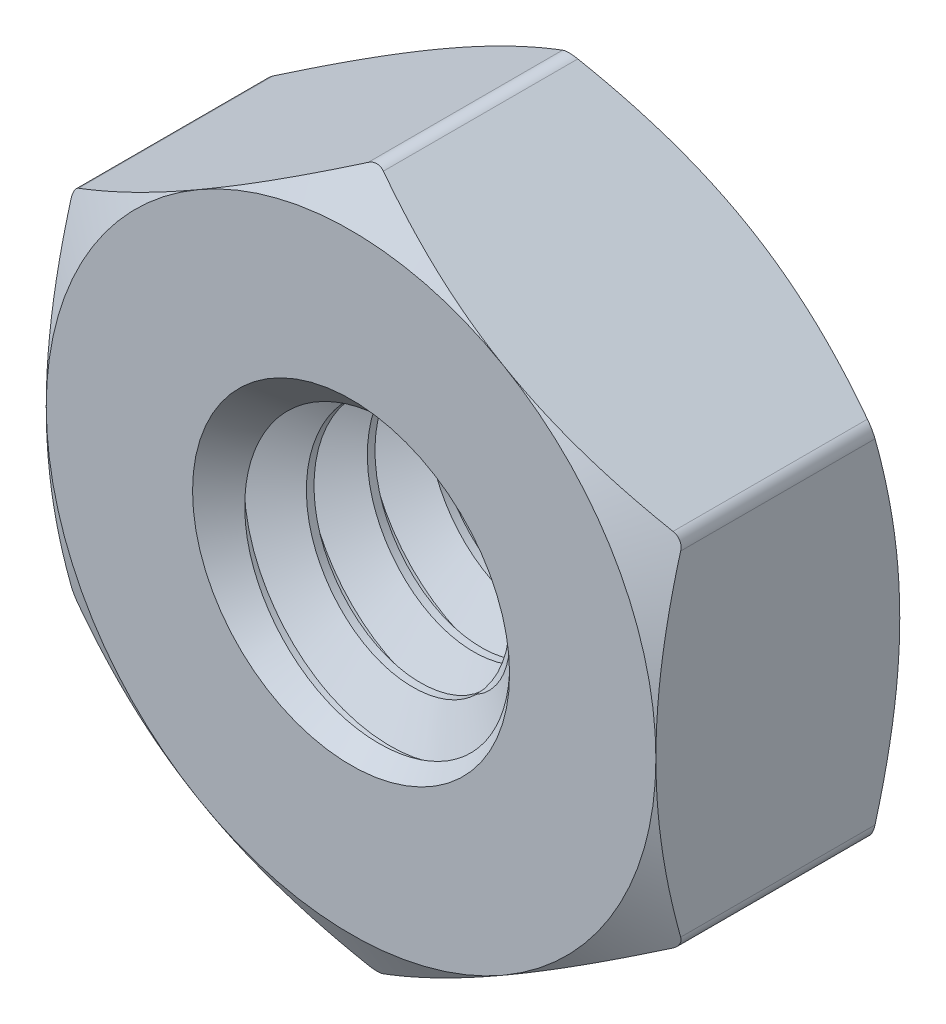
SolidWorks part; units mm, degrees
ref_plane "Front" through (0, 0, 0) normal (0, 0, 1) x (1, 0, 0)
ref_plane "Top" through (0, 0, 0) normal (0, 1, 0) x (1, 0, 0)
ref_plane "Right" through (0, 0, 0) normal (1, 0, 0) x (0, 0, -1)
sketch "Sketch1" plane through (0, 0, 0) normal (0, 0, 1) x (1, 0, 0)
  line L0 (0, 1) -> (0, 0.6) construction
  line L1 (-2, 1.1547) -> (-2, -1.1547)
  line L2 (-2, -1.1547) -> (0, -2.3094)
  line L3 (0, -2.3094) -> (2, -1.1547)
  line L4 (2, -1.1547) -> (2, 1.1547)
  line L5 (2, 1.1547) -> (0, 2.3094)
  line L6 (0, 2.3094) -> (-2, 1.1547)
  circle A0 centre (0, 0) radius 2 construction
  circle A1 centre (0, 0) radius 1 construction
  point P10 (0, 1)
  dimension "Width" = 4
  dimension "Thread Size" = 2
  dimension "Thread Pitch" = 0.4
sketch "Sketch2" plane through (0, 0, 0) normal (1, 0, 0) x (0, 0, -1)
  line L0 (-0.8, 0) -> (0.8, 0) construction
  line L1 (-0.8, 2.3094) -> (0.8, 2.3094) construction
  dimension "Height" = 1.6
sketch "Sketch15" plane through (0, 0, 0) normal (0, 0, 1) x (1, 0, 0)
  line L1 (0, 2.3094) -> (-2, 1.1547)
  line L2 (-2, 1.1547) -> (-2, -1.1547)
  line L3 (-2, -1.1547) -> (0, -2.3094)
  line L4 (0, -2.3094) -> (2, -1.1547)
  line L5 (2, -1.1547) -> (2, 1.1547)
  line L6 (2, 1.1547) -> (0, 2.3094)
  circle A0 centre (0, 0) radius 2 construction
extrude "Boss-Extrude2" add sketch "Sketch15" along normal mid plane 1.6
sketch "Sketch16" plane through (0, 0, 0) normal (0, 0, 1) x (1, 0, 0)
  circle A0 centre (0, 0) radius 1 construction
  circle A1 centre (0, 0) radius 1
sketch "Sketch4" plane through (0, 0, -0.8) normal (0, 0, -1) x (-1, 0, 0)
  circle A0 centre (0, 0) radius 1 construction
  circle A1 centre (0, 0) radius 1
extrude "Cut-Extrude4" cut sketch "Sketch16" against normal through all both and the other way through all
sketch "Sketch7" plane through (0, 0, 0.8) normal (0, 0, 1) x (1, 0, 0)
  circle A0 centre (0, 0) radius 2 construction
  circle A1 centre (0, 0) radius 2
extrude "Cut-Extrude5" cut sketch "Sketch7" against normal through all draft 60 flip side to cut
mirror "Mirror4" about plane through (0, 0, 0) normal (0, 0, 1) of "Cut-Extrude5"
fillet "Fillet2" radius 0.1 6 edges at (-2, 1.1547, 0) (-2, -1.1547, 0) (0, -2.3094, 0) (2, -1.1547, 0) (2, 1.1547, 0) (0, 2.3094, 0)
sketch "Sketch8" plane through (0, 0, 0.8) normal (0, 0, 1) x (1, 0, 0)
  line L0 (0.2588, -0.9659) -> (0, 0) construction
  line L2 (0, 1) -> (0, 0.6) construction
  circle A0 centre (0, 0) radius 1 construction
  point P0 (0.2588, -0.9659)
  dimension "D1" = 15
sketch "Sketch13" plane through (0, 0, -0.8) normal (0, 0, -1) x (-1, 0, 0)
  circle A0 centre (0, 0) radius 1 construction
  circle A1 centre (0, 0) radius 1
extrude "Boss-Extrude1" add sketch "Sketch13" against normal up to surface (1.6 mm away) separate body up to face at (1, 0, 0.8)
curve "Helix/Spiral3" pitch 0.4 height 2.4 radius 1 centre (0, 0, -0.8) axis (0, 0, 1) start towards (0, 1, 0)
sketch "Sketch12" plane through (0, 0, 0) normal (1, 0, 0) x (0, 0, -1)
  line L0 (1.15, 1) -> (0.8, 1)
  line L1 (1.15, 1) -> (1, 0.7402)
  line L2 (1, 0.7402) -> (0.95, 0.7402)
  line L3 (0.95, 0.7402) -> (0.8, 1)
  line L4 (0.975, 0.7402) -> (0.975, 1) construction
  line L5 (0.875, 0.8701) -> (1.075, 0.8701) construction
  dimension "D1" = 60
  dimension "D2" = 0.05
  dimension "D3" = 0.2
sweep "Cut-Sweep1" cut profiles "Sketch12" path "Helix/Spiral3" align with end faces yes
sketch "Sketch17" plane through (0, 0, 0.8) normal (0, 0, 1) x (1, 0, 0)
  circle A1 centre (0, 0) radius 1
  circle A2 centre (0, 0) radius 1
  dimension "D1" = 0
extrude "Boss-Extrude3" add sketch "Sketch17" against normal up to surface (1.6 mm away) up to face at (1, 0, -0.8)
combine bodies "Combine1" operation type subtract main body 127 bodies to subtract 118
sketch "Sketch10" plane through (0, 0, 0.8) normal (0, 0, 1) x (1, 0, 0)
  circle A0 centre (0, 0) radius 1 construction
  circle A1 centre (0, 0) radius 1 construction
  circle A2 centre (0, 0) radius 1.04
  dimension "D1" = 0.04
extrude "Cut-Extrude2" cut sketch "Sketch10" against normal through all draft 45
sketch "Sketch11" plane through (0, 0, -0.8) normal (0, 0, -1) x (-1, 0, 0)
  circle A1 centre (0, 0) radius 1.04 construction
  circle A2 centre (0, 0) radius 1.04
extrude "Cut-Extrude3" cut sketch "Sketch11" against normal through all draft 45
equation "\"D1\"= \"Height@Sketch2\""
equation "\"D3@Helix/Spiral3\"=\"Height@Sketch2\"+\"Thread Pitch@Sketch1\"*2"
equation "\"D4@Helix/Spiral3\"=\"Thread Pitch@Sketch1\""
equation "\"D2@Sketch12\" = \"D4@Helix/Spiral3\"*.125"
equation "\"D3@Sketch12\" = \"D4@Helix/Spiral3\"*.50"
equation "\"D1@Boss-Extrude2\"=\"Height@Sketch2\""
equation "\"D1@Fillet2\"=\"Width@Sketch1\"*0.025"
equation "\"D1@Sketch10\"=\"Thread Pitch@Sketch1\"*0.1"
